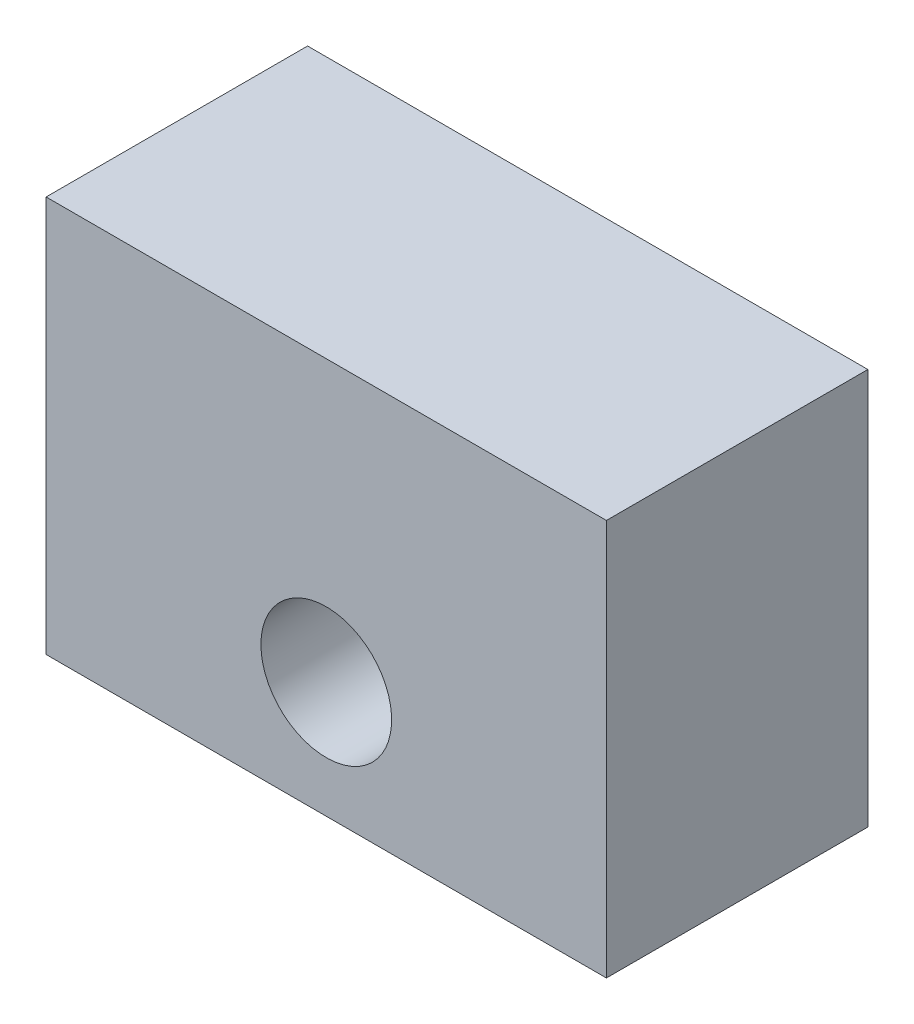
SolidWorks part; units mm, degrees
ref_plane "Front Plane" through (0, 0, 0) normal (0, 0, 1) x (1, 0, 0)
ref_plane "Top Plane" through (0, 0, 0) normal (0, 1, 0) x (1, 0, 0)
ref_plane "Right Plane" through (0, 0, 0) normal (1, 0, 0) x (0, 0, -1)
sketch "Sketch1" plane through (0, 0, 0) normal (0, 1, 0) x (1, 0, 0)
  line L1 (-7.5, 30) -> (7.5, 30)
  line L2 (-7.5, 30) -> (-7.5, -30)
  line L3 (-7.5, -30) -> (7.5, -30)
  line L4 (7.5, 30) -> (7.5, -30)
  line L5 (-7.5, 30) -> (7.5, -30) construction
  line L6 (-7.5, -30) -> (7.5, 30) construction
  point P0 (0, 0)
  dimension "D1" = 15
  dimension "D2" = 60
extrude "Boss-Extrude2" add sketch "Sketch1" along normal blind 39.11
sketch "Sketch3" plane through (-7.5, 0, 0) normal (-1, 0, 0) x (0, 0, 1)
  line L0 (-30, 0) -> (30, 0)
  line L1 (-30, 0) -> (-30, 5)
  line L2 (30, 0) -> (30, 5)
  line L3 (-30, 5) -> (30, 5)
  dimension "D1" = 5
extrude "Boss-Extrude3" add sketch "Sketch3" along normal blind 12 and the other way blind 27
ref_plane "Plane1" through (0, 0, 0) normal (0, 0, 1) x (1, 0, 0)
sketch "Sketch5" plane through (0, 0, 0) normal (0, 0, 1) x (1, 0, 0)
  line L0 (-7.5, 22.055) -> (-16.5741, 5)
  line L1 (-7.5, 39.11) -> (-7.5, 5) construction
  line L2 (-7.5, 5) -> (-19.5, 5) construction
rib "Rib1" sketch "Sketch5" sketch "Sketch5" thickness 10 extrusion direction parallel to sketch draft on no parameters "D1"=10
sketch "Sketch6" plane through (0, 5, 0) normal (0, 1, 0) x (1, 0, 0)
  line L0 (-19.5, -30) -> (-19.5, 30) construction
  line L1 (-7.5, -30) -> (-19.5, -30) construction
  line L2 (-18.15, 0) -> (18.15, 0) construction
  circle A0 centre (-14.5, -25) radius 1.5
  circle A1 centre (-14.5, 25) radius 1.5
  dimension "D1" = 3
  dimension "D2" = 5
  dimension "D3" = 5
extrude "Cut-Extrude2" cut sketch "Sketch6" against normal through all
mirror "Mirror1" about plane through (0, 0, 0) normal (1, 0, 0) of "Rib1", "Cut-Extrude2"
sketch "Sketch7" plane through (-7.5, 0, 0) normal (-1, 0, 0) x (0, 0, 1)
  line L0 (-30, 39.11) -> (30, 39.11) construction
  line L1 (7, 39.11) -> (23, 39.11)
  line L2 (7, 39.11) -> (7, 23.11)
  line L3 (7, 23.11) -> (23, 23.11)
  line L4 (23, 39.11) -> (23, 23.11)
  line L5 (7, 39.11) -> (23, 23.11) construction
  line L6 (7, 23.11) -> (23, 39.11) construction
  line L7 (30, 39.11) -> (30, 5) construction
  point P0 (15, 31.11)
  dimension "D1" = 16
  dimension "D2" = 16
  dimension "D3" = 7
extrude "Cut-Extrude3" cut sketch "Sketch7" against normal through all
mirror "Mirror2" about plane through (0, 0, 0) normal (0, 0, 1) of "Cut-Extrude3"
sketch "Sketch8" plane through (0, 0, -30) normal (0, 0, -1) x (-1, 0, 0)
  line L0 (-7.5, 39.11) -> (7.5, 39.11) construction
  circle A0 centre (0, 31.61) radius 1.75
  dimension "D2" = 3.5
  dimension "D1" = 7.5
extrude "Cut-Extrude4" cut sketch "Sketch8" against normal through all
fillet "Fillet1" radius 3 10 edges at (19.5, 2.5, -30) (19.5, 2.5, 30) (-19.5, 2.5, 30) (-19.5, 2.5, -30) (-16.5741, 5, 0) (-7.5, 5, -17.5) (-7.5, 5, 17.5) (16.5741, 5, 0) (7.5, 5, 17.5) (7.5, 5, -17.5)
sketch "Sketch10" plane through (0, 0, 30) normal (0, 0, 1) x (1, 0, 0)
  line L0 (7.5, 28.5011) -> (-7.5, 28.5011)
  line L1 (7.5, 39.11) -> (7.5, 8) construction
  line L2 (-7.5, 39.11) -> (-7.5, 8) construction
  line L3 (-7.5, 28.5011) -> (-22.2205, 28.5011)
  line L4 (-22.2205, 28.5011) -> (-22.2205, 0)
  line L5 (-22.2205, 0) -> (19.5, 0)
  line L6 (19.5, 0) -> (19.5, 28.5011)
  line L7 (19.5, 28.5011) -> (7.5, 28.5011)
extrude "Cut-Extrude5" cut sketch "Sketch10" against normal through all
sketch "Sketch11" plane through (0, 0, 23) normal (0, 0, -1) x (-1, 0, 0)
  line L0 (-7.5, 39.11) -> (-7.5, 28.5011)
  line L1 (-7.5, 28.5011) -> (7.5, 28.5011)
  line L2 (7.5, 28.5011) -> (7.5, 39.11)
  line L3 (7.5, 39.11) -> (-7.5, 39.11)
extrude "Cut-Extrude6" cut sketch "Sketch11" along normal through all
